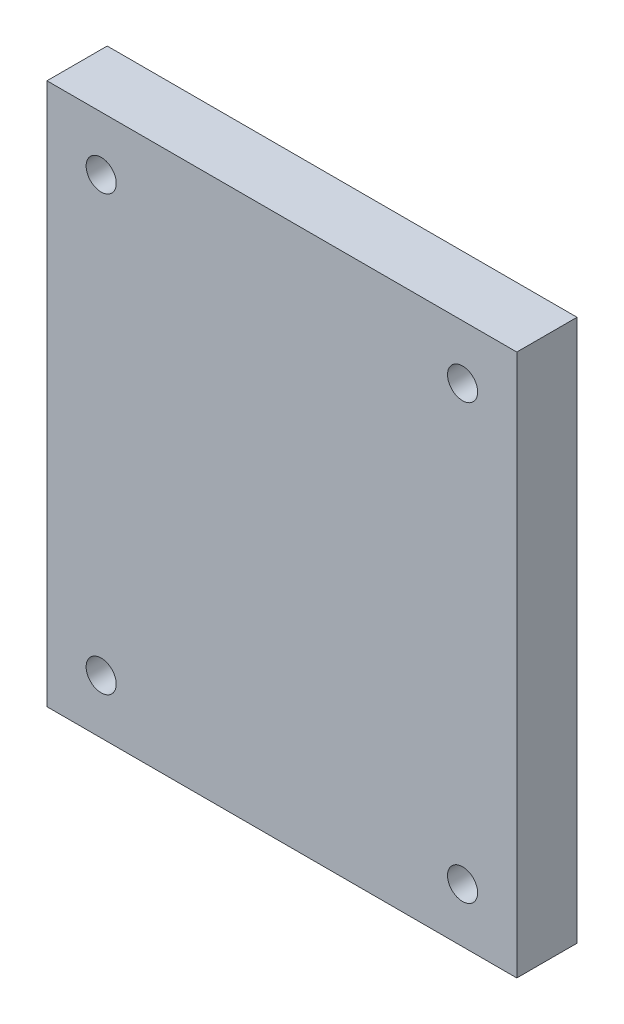
SolidWorks part; units mm, degrees
ref_plane "Front Plane" through (0, 0, 0) normal (0, 0, 1) x (1, 0, 0)
ref_plane "Top Plane" through (0, 0, 0) normal (0, 1, 0) x (1, 0, 0)
ref_plane "Right Plane" through (0, 0, 0) normal (1, 0, 0) x (0, 0, -1)
sketch "Sketch1" plane through (0, 0, 0) normal (0, 0, 1) x (1, 0, 0)
  line L0 (0, -1000) -> (0, 49000) construction
  line L1 (-19.5, 22.5) -> (19.5, 22.5)
  line L2 (-19.5, 22.5) -> (-19.5, -22.5)
  line L3 (-19.5, -22.5) -> (19.5, -22.5)
  line L4 (19.5, 22.5) -> (19.5, -22.5)
  line L5 (-1000, 0) -> (49000, 0) construction
  circle A0 centre (-15, 18) radius 1.25
  circle A1 centre (15, 18) radius 1.25
  circle A2 centre (15, -18) radius 1.25
  circle A3 centre (-15, -18) radius 1.25
  dimension "D1" = 2.5
extrude "Boss-Extrude1" add sketch "Sketch1" along normal blind 5 contours L4 L1 L2 L3 A1 A0 A2 A3 region at (0, 0, 0)
